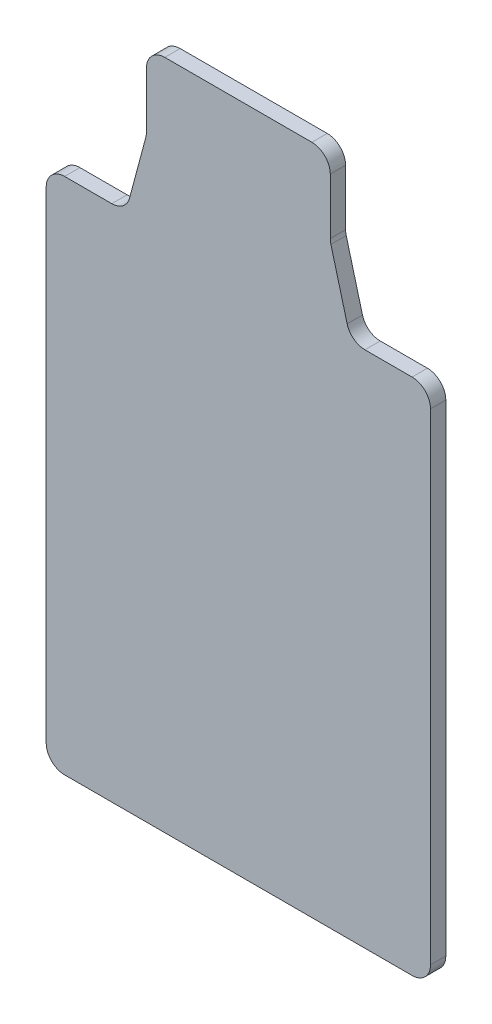
SolidWorks part; units mm, degrees
material "Thornel Mat VMA"
ref_plane "Front Plane" through (0, 0, 0) normal (0, 0, 1) x (1, 0, 0)
ref_plane "Top Plane" through (0, 0, 0) normal (0, 1, 0) x (1, 0, 0)
ref_plane "Right Plane" through (0, 0, 0) normal (1, 0, 0) x (0, 0, -1)
sketch "Sketch1" plane through (0, 0, 0) normal (0, 0, 1) x (1, 0, 0)
  line L0 (0, 42.2818) -> (0, 67.2818) construction
  line L5 (-31.35, 42.2818) -> (31.35, 42.2818)
  line L6 (-31.35, 42.2818) -> (-31.35, -42.2818)
  line L12 (-31.35, -42.2818) -> (31.35, -42.2818)
  line L17 (31.35, 42.2818) -> (31.35, -42.2818)
  line L19 (-31.35, 42.2818) -> (31.35, -42.2818) construction
  line L20 (-31.35, -42.2818) -> (31.35, 42.2818) construction
  line L21 (-15, 67.2818) -> (15, 67.2818)
  line L22 (-15, 67.2818) -> (-15, 54.7818)
  line L23 (-15, 54.7818) -> (-18.3494, 42.2818)
  line L24 (15, 54.7818) -> (18.3494, 42.2818)
  line L25 (15, 67.2818) -> (15, 54.7818)
  point P0 (0, 0)
  point P10 (0, 67.2818)
  point P11 (-10, 50.143)
  dimension "D1" = 62.7
  dimension "D2" = 84.5637
  dimension "D3" = 75
  dimension "D4" = 30
  dimension "D5" = 25
  dimension "D6" = 12.5
extrude "Boss-Extrude1" add sketch "Sketch1" along normal mid plane 2.5 contours L25 L21 L22 L23 L5 L24 | L17 L5 L6 L12 region at (0, 0, 0) region at (0, 54.3412, 0)
fillet "Fillet1" radius 3 10 edges at (15, 54.7818, 0) (18.3494, 42.2818, 0) (31.35, 42.2818, 0) (31.35, -42.2818, 0) (-31.35, -42.2818, 0) (15, 67.2818, 0) (-15, 67.2818, 0) (-31.35, 42.2818, 0) (-15, 54.7818, 0) (-18.3494, 42.2818, 0)
